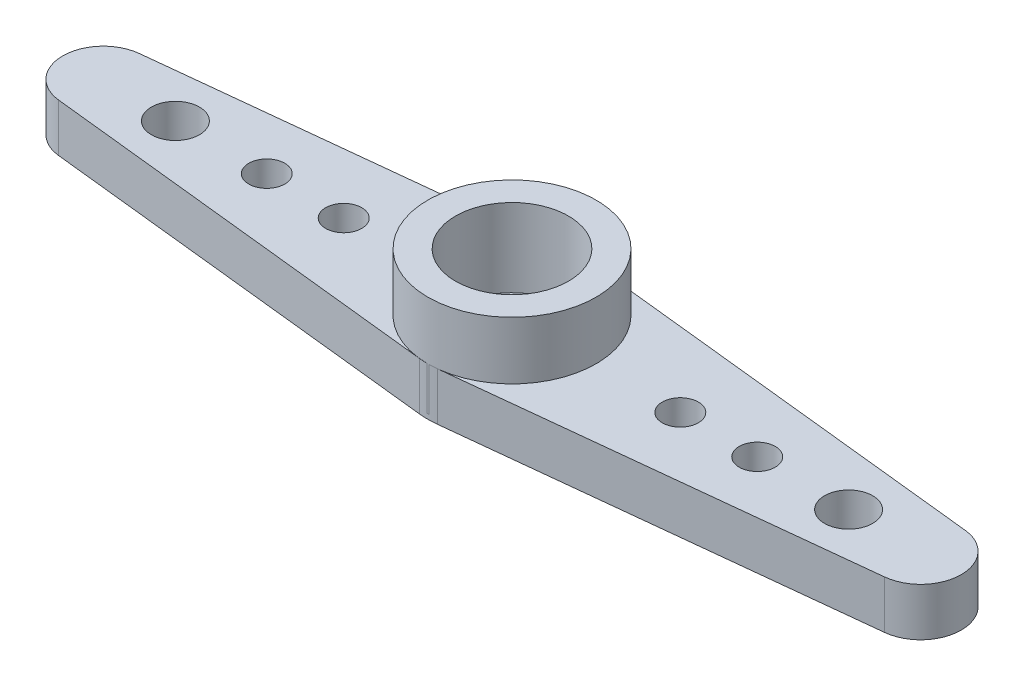
SolidWorks part; units mm, degrees
ref_plane "Front Plane" through (0, 0, 0) normal (0, 0, 1) x (1, 0, 0)
ref_plane "Top Plane" through (0, 0, 0) normal (0, 1, 0) x (1, 0, 0)
ref_plane "Right Plane" through (0, 0, 0) normal (1, 0, 0) x (0, 0, -1)
sketch "Sketch1" plane through (0, 0, 0) normal (0, 1, 0) x (1, 0, 0)
  circle A0 centre (0, 0) radius 3.5
  circle A1 centre (0, 0) radius 1.5
extrude "Boss-Extrude1" add sketch "Sketch1" along normal blind 4.2 from offset 0.2 offset against normal yes
sketch "Sketch2" plane through (0, -0.2, 0) normal (0, -1, 0) x (1, 0, 0)
  line L0 (0, 0) -> (0, -7.0493) construction
  line L1 (-0.3733, 3.48) -> (-17.1799, 1.6774)
  line L2 (0.3733, 3.48) -> (17.1799, 1.6774)
  line L3 (-0.5833, -3.451) -> (-17.1793, -1.6774)
  line L4 (0.5833, -3.451) -> (17.1793, -1.6774)
  arc A0 (0.3733, 3.48) -> (-0.3733, 3.48) centre (0, 0) ccw
  arc A1 (17.1793, -1.6774) -> (17.1799, 1.6774) centre (17, 0) ccw
  circle A2 centre (0, 0) radius 1.5
  circle A3 centre (14, 0) radius 1
  arc A4 (-0.5833, -3.451) -> (0.5833, -3.451) centre (0, 0) ccw
  arc A5 (-17.1793, -1.6774) -> (-17.1799, 1.6774) centre (-17, 0) cw
  circle A6 centre (-14, 0) radius 1
  dimension "D2" = 14
  dimension "D1" = 17
extrude "Boss-Extrude2" add sketch "Sketch2" against normal blind 2 from offset 0.2 separate body
sketch "Sketch3" plane through (0, 4, 0) normal (0, 1, 0) x (1, 0, 0)
  circle A0 centre (0, 0) radius 2.35
extrude "Cut-Extrude1" cut sketch "Sketch3" against normal blind 3.25
sketch "Sketch5" plane through (0, -0.4, 0) normal (0, -1, 0) x (1, 0, 0)
  line L0 (0, 0) -> (0, -11.2896) construction
  circle A0 centre (10.2, 0) radius 0.75
  circle A1 centre (7, 0) radius 0.75
  circle A2 centre (-7, 0) radius 0.75
  circle A3 centre (-10.2, 0) radius 0.75
  dimension "D1" = 3.2
  dimension "D2" = 7
extrude "Cut-Extrude2" cut sketch "Sketch5" against normal through all
